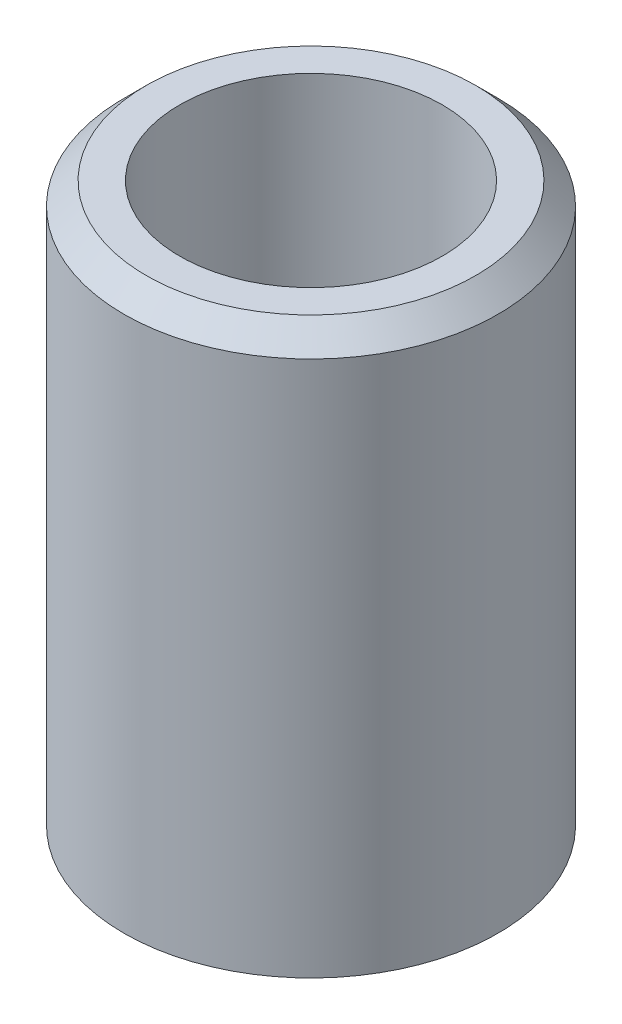
SolidWorks part; units mm, degrees
material "Brass"
ref_plane "Front Plane" through (0, 0, 0) normal (0, 0, 1) x (1, 0, 0)
ref_plane "Top Plane" through (0, 0, 0) normal (0, 1, 0) x (1, 0, 0)
ref_plane "Right Plane" through (0, 0, 0) normal (1, 0, 0) x (0, 0, -1)
sketch "Sketch2" plane through (0, 0, 0) normal (0, 0, 1) x (1, 0, 0)
  line L0 (0, 0) -> (0, 51.583) construction
  line L2 (-8.375, 0) -> (-5.875, 0)
  line L3 (-8.375, 0) -> (-8.375, 25)
  line L4 (-8.375, 25) -> (-5.875, 25)
  line L5 (-5.875, 0) -> (-5.875, 25)
  dimension "D1" = 5.875
  dimension "D2" = 2.5
  dimension "25" = 25
revolve "Revolve1" add sketch "Sketch2" angle 360 about L0
chamfer "Chamfer1" distance 1 angle 45 1 edges at (0, 25, -8.375)
equation "\"D1@Sketch2\"=(11.7+0.05)/2"
